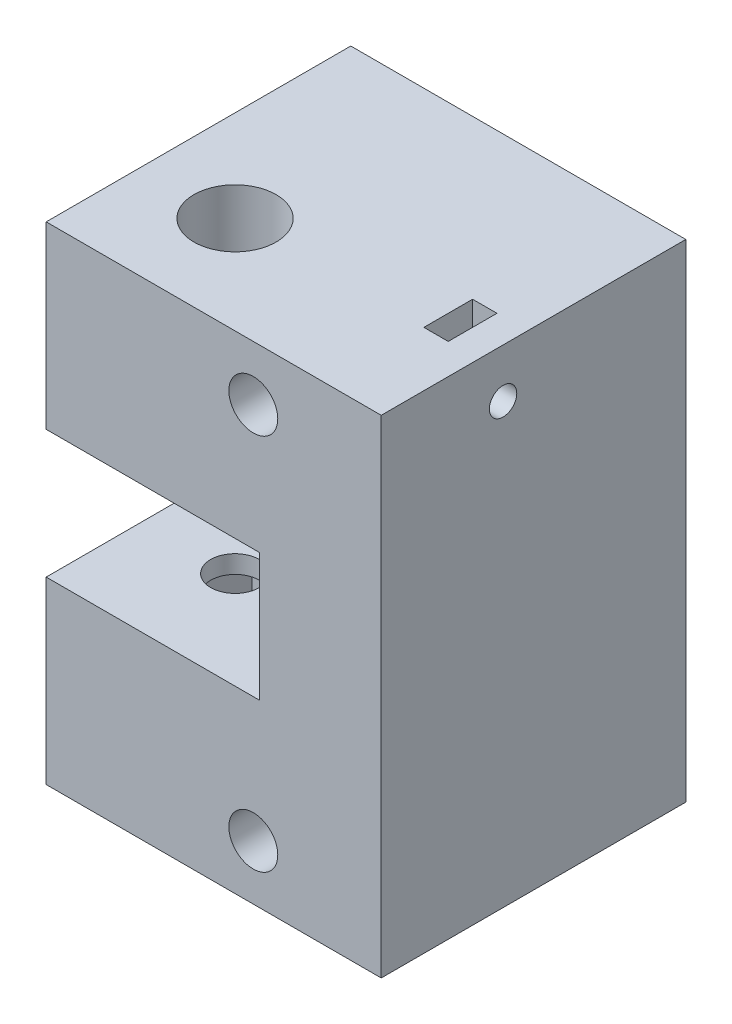
SolidWorks part; units mm, degrees
ref_plane "Front Plane" through (0, 0, 0) normal (0, 0, 1) x (1, 0, 0)
ref_plane "Top Plane" through (0, 0, 0) normal (0, 1, 0) x (1, 0, 0)
ref_plane "Right Plane" through (0, 0, 0) normal (1, 0, 0) x (0, 0, -1)
sketch "Sketch1" plane through (0, 0, 0) normal (0, 0, 1) x (1, 0, 0)
  line L1 (0, 0) -> (-55, 0)
  line L2 (0, 0) -> (0, 80)
  line L3 (0, 80) -> (-55, 80)
  line L4 (-55, 0) -> (-55, 80)
  dimension "D1" = 55
  dimension "D2" = 80
extrude "Boss-Extrude1" add sketch "Sketch1" along normal blind 50
sketch "Sketch2" plane through (0, 80, 0) normal (0, 1, 0) x (1, 0, 0)
  line L0 (0, -50) -> (-42, -50) construction
  line L1 (0, -50) -> (-55, -50) construction
  line L2 (-21, -50) -> (-21, -39.0192) construction
  circle A0 centre (-40, -34) radius 4
  dimension "D2" = 8
  dimension "D1" = 42
  dimension "D3" = 19
  dimension "D4" = 16
extrude "Cut-Extrude1" cut sketch "Sketch2" against normal through all
sketch "Sketch3" plane through (0, 0, 50) normal (0, 0, 1) x (1, 0, 0)
  line L0 (0, 0) -> (-42, 0) construction
  line L1 (-55, 0) -> (0, 0) construction
  line L2 (-21, 0) -> (-21, 9.4631) construction
  line L3 (0, 80) -> (-55, 80) construction
  circle A0 centre (-21, 71) radius 4.015
  circle A1 centre (-21, 9) radius 4.015
  dimension "D2" = 8.03
  dimension "D1" = 42
  dimension "D3" = 9
  dimension "D4" = 9
extrude "Cut-Extrude2" cut sketch "Sketch3" against normal blind 8.03
sketch "Sketch4" plane through (0, 0, 50) normal (0, 0, 1) x (1, 0, 0)
  line L0 (-55, 80) -> (-55, 0) construction
  line L1 (-55, 29.5) -> (-20, 29.5)
  line L2 (-55, 29.5) -> (-55, 50.5)
  line L3 (-55, 50.5) -> (-20, 50.5)
  line L4 (-20, 29.5) -> (-20, 50.5)
  line L5 (0, 40) -> (-13.6751, 40) construction
  line L6 (0, 0) -> (0, 80) construction
  point P10 (-20, 40)
  dimension "D1" = 21
  dimension "D2" = 35
extrude "Cut-Extrude3" cut sketch "Sketch4" against normal blind 35
sketch "Sketch8" plane through (0, 80, 0) normal (0, 1, 0) x (1, 0, 0)
  circle A0 centre (-40, -34) radius 6.75
  circle A1 centre (-40, -34) radius 4 construction
  dimension "D1" = 13.5
extrude "Cut-Extrude5" cut sketch "Sketch8" against normal offset from surface (26.55 mm away) 2.95 up to face at (-37.5, 50.5, 32.5)
sketch "Sketch9" plane through (0, 0, 0) normal (0, -1, 0) x (1, 0, 0)
  line L1 (-32.4367, 34) -> (-36.2184, 40.55)
  line L2 (-36.2184, 40.55) -> (-43.7816, 40.55)
  line L3 (-43.7816, 40.55) -> (-47.5633, 34)
  line L4 (-47.5633, 34) -> (-43.7816, 27.45)
  line L5 (-43.7816, 27.45) -> (-36.2184, 27.45)
  line L6 (-36.2184, 27.45) -> (-32.4367, 34)
  circle A0 centre (-40, 34) radius 6.55 construction
  dimension "D1" = 13.1
extrude "Cut-Extrude6" cut sketch "Sketch9" against normal offset from surface (26.55 mm away) 2.95 up to face at (-37.5, 29.5, 32.5)
ref_plane "Plane1" through (-35, 0, 0) normal (-1, 0, 0) x (0, 0, 1)
ref_plane "Plane2" through (0, 0, 30) normal (0, 0, 1) x (1, 0, 0)
sketch "Sketch10" plane through (0, 0, 0) normal (0, -1, 0) x (1, 0, 0)
  line L0 (-55, 50) -> (-55, 0) construction
  line L1 (-55, 50) -> (0, 50) construction
  circle A0 centre (-12.5, 7.5) radius 2
  circle A1 centre (-12.5, 22.5) radius 2
  dimension "D4" = 4
  dimension "D1" = 15
  dimension "D2" = 42.5
  dimension "D3" = 42.5
extrude "Cut-Extrude7" cut sketch "Sketch10" against normal blind 5
sketch "Sketch12" plane through (0, 0, 15) normal (0, 0, 1) x (1, 0, 0)
  line L0 (-20, 40) -> (-35, 40) construction
  line L1 (-20, 29.5) -> (-20, 50.5) construction
  line L2 (-55, 50.5) -> (-55, 29.5) construction
  circle A0 centre (-47.5, 40) radius 3.75
  circle A1 centre (-27.5, 40) radius 3.75
  circle A2 centre (-47.5, 40) radius 2.1
  circle A3 centre (-27.5, 40) radius 2.1
  dimension "D3" = 7.5
  dimension "D4" = 4.2
  dimension "D1" = 20
  dimension "D2" = 7.5
extrude "Cut-Extrude8" cut sketch "Sketch12" against normal through all contours A2 | L0 A3 | A3 L0 region at (-27.5, 39.1087, 15) region at (-27.5, 40.8913, 15) region at (-47.5, 40, 15)
extrude "Cut-Extrude9" cut sketch "Sketch12<3>" against normal blind 4.5 contours L0 A1 A3 | A1 L0 A3 | A0 region at (-27.5, 36.3339, 15) region at (-24.575, 40.0839, 15)
sketch "Sketch12<3>" plane through (0, 0, 15) normal (0, 0, 1) x (1, 0, 0) same geometry as "Sketch12"
sketch "Sketch13" plane through (0, 0, 0) normal (1, 0, 0) x (0, 0, -1)
  line L0 (-50, 80) -> (0, 80) construction
  circle A0 centre (-30, 72) radius 2.25
  dimension "D3" = 4.5
  dimension "D1" = 30
  dimension "D2" = 8
extrude "Cut-Extrude10" cut sketch "Sketch13" against normal blind 10
sketch "Sketch14" plane through (0, 80, 0) normal (0, 1, 0) x (1, 0, 0)
  line L0 (0, -50) -> (0, 0) construction
  line L1 (-5, -34) -> (-9, -34)
  line L2 (-5, -34) -> (-5, -26)
  line L3 (-5, -26) -> (-9, -26)
  line L4 (-9, -34) -> (-9, -26)
  point P6 (-9, -30)
  point P7 (-5, -30)
  dimension "D1" = 5
  dimension "D2" = 4
  dimension "D3" = 30
  dimension "D4" = 8
extrude "Cut-Extrude11" cut sketch "Sketch14" against normal blind 13
sketch "Sketch15" plane through (-55, 0, 0) normal (-1, 0, 0) x (0, 0, 1)
  line L0 (50, 65.25) -> (0, 65.25) construction
  line L1 (50, 80) -> (50, 50.5) construction
  line L2 (0, 80) -> (0, 0) construction
  text T0 "A" font "Century Gothic" height 10
extrude "Cut-Extrude12" cut sketch "Sketch15" against normal blind 0.5
